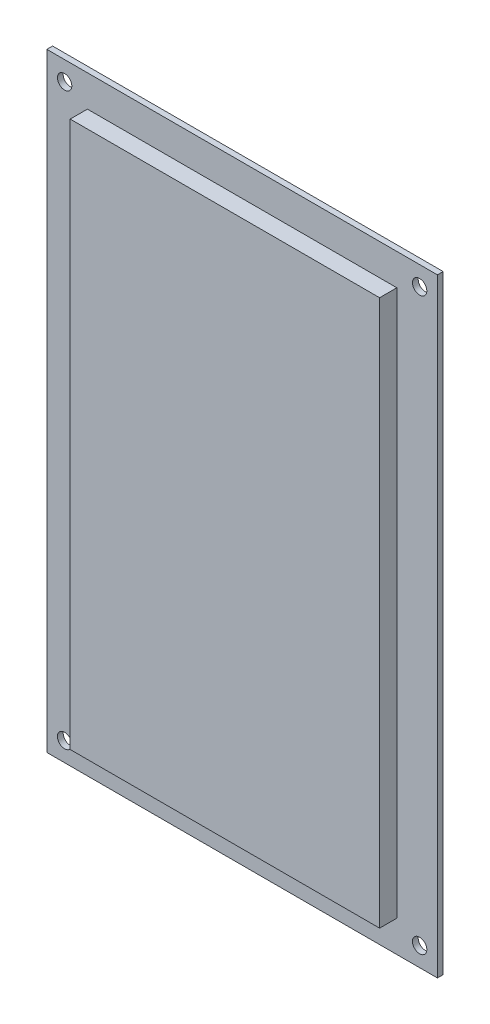
SolidWorks part; units mm, degrees
ref_plane "Front Plane" through (0, 0, 0) normal (0, 0, 1) x (1, 0, 0)
ref_plane "Top Plane" through (0, 0, 0) normal (0, 1, 0) x (1, 0, 0)
ref_plane "Right Plane" through (0, 0, 0) normal (1, 0, 0) x (0, 0, -1)
sketch "Sketch2" plane through (0, 0, 0) normal (0, 0, 1) x (1, 0, 0)
  line L0 (-20.017, 37.185) -> (33.843, 37.185) construction
  line L1 (-20.017, 43.585) -> (33.843, 43.585)
  line L2 (-20.017, 43.585) -> (-20.017, -51.455)
  line L3 (-20.017, -51.455) -> (33.843, -51.455)
  line L4 (33.843, 43.585) -> (33.843, -51.455)
  line L5 (-20.017, -41.055) -> (33.843, -41.055) construction
  line L6 (6.913, 43.585) -> (6.913, -51.455) construction
  dimension "D1" = 95.04
  dimension "D2" = 53.86
  dimension "D3" = 6.4
  dimension "D4" = 10.4
extrude "Boss-Extrude1" add sketch "Sketch2" along normal blind 3
sketch "Sketch3" plane through (0, 0, 0) normal (0, 0, -1) x (-1, 0, 0)
  line L0 (-6.913, -51.455) -> (-6.913, 43.585) construction
  line L1 (20.017, -51.455) -> (-33.843, -51.455) construction
  line L2 (-33.843, 43.585) -> (20.017, 43.585) construction
  line L3 (-33.843, -3.935) -> (20.017, -3.935) construction
  line L4 (-33.843, -51.455) -> (-33.843, 43.585) construction
  line L5 (20.017, 43.585) -> (20.017, -51.455) construction
  line L6 (-49.2074, -53.585) -> (-49.2074, -51.455) construction
  line L7 (-40.913, 49.065) -> (27.087, 49.065)
  line L8 (-40.913, 49.065) -> (-40.913, -56.935)
  line L9 (-40.913, -56.935) -> (27.087, -56.935)
  line L10 (27.087, 49.065) -> (27.087, -56.935)
  line L11 (-40.913, 49.065) -> (27.087, -56.935) construction
  line L12 (-40.913, -56.935) -> (27.087, 49.065) construction
  line L13 (-55.5095, 45.715) -> (-55.5095, 43.585) construction
  line L14 (20.017, 43.585) -> (-33.843, 43.585) construction
  line L15 (-33.843, -51.455) -> (20.017, -51.455) construction
  circle A0 centre (23.987, 45.715) radius 1.25
  circle A1 centre (23.987, -53.585) radius 1.25
  circle A2 centre (-37.813, 45.715) radius 1.25
  circle A3 centre (-37.813, -53.585) radius 1.25
  point P12 (-6.913, -3.935)
  point P31 (0, 0)
  point P37 (0, 0)
  point P38 (0, 0)
  dimension "D1" = 2.5
  dimension "D2" = 106
  dimension "D3" = 68
  dimension "D4" = 61.8
  dimension "D5" = 99.3
extrude "Boss-Extrude2" add sketch "Sketch3" along normal blind 1
